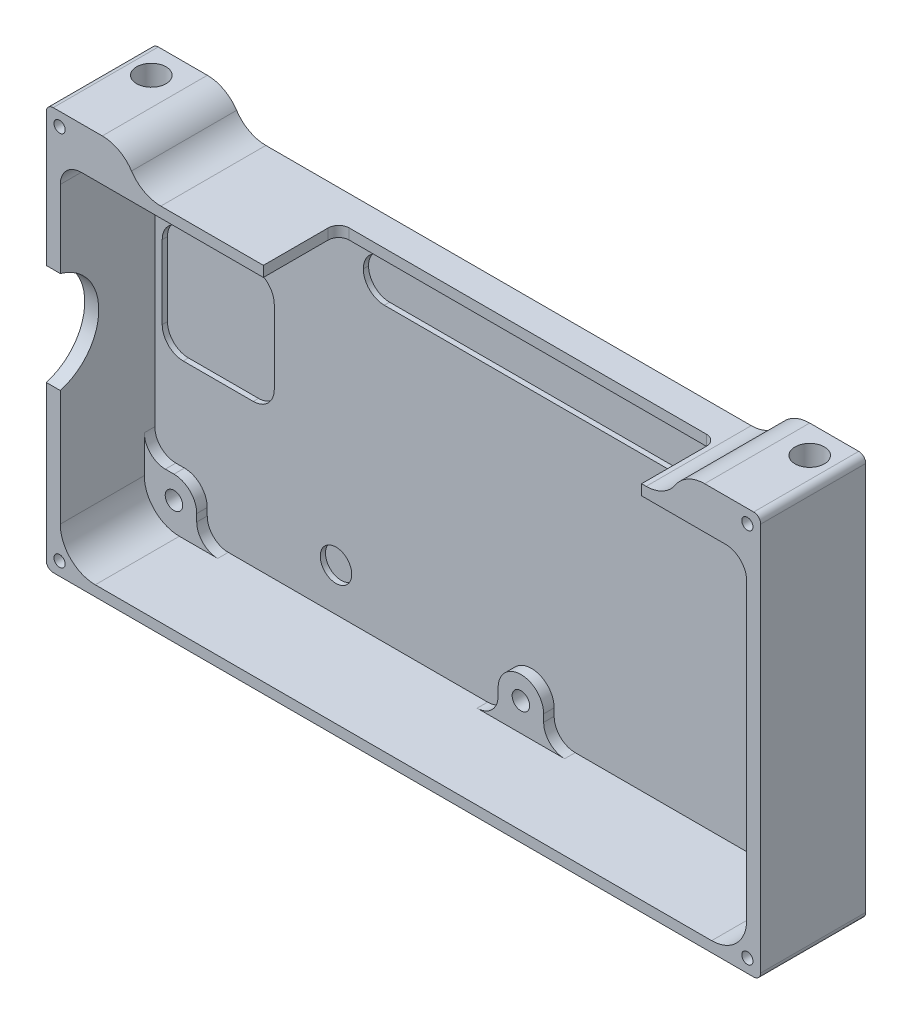
SolidWorks part; units mm, degrees
material "7075-T6, Platte (SS)"
ref_plane "Ebene vorne" through (0, 0, 0) normal (0, 0, 1) x (1, 0, 0)
ref_plane "Ebene oben" through (0, 0, 0) normal (0, 1, 0) x (1, 0, 0)
ref_plane "Ebene rechts" through (0, 0, 0) normal (1, 0, 0) x (0, 0, -1)
sketch "Skizze1" plane through (0, 0, 0) normal (0, 0, 1) x (1, 0, 0)
  line L1 (0, 0) -> (102, 0)
  line L2 (0, 0) -> (0, 57.5)
  line L3 (0, 57.5) -> (102, 57.5)
  line L4 (102, 0) -> (102, 57.5)
  line L5 (2, 51.5) -> (100, 51.5) construction
  line L6 (2, 51.5) -> (2, 1.5)
  line L7 (2, 1.5) -> (100, 1.5) construction
  line L8 (100, 51.5) -> (100, 1.5) construction
  dimension "D1" = 2
  dimension "D2" = 2
  dimension "D3" = 6
  dimension "D4" = 1.5
  dimension "D5" = 50
  dimension "D6" = 98
extrude "Aufsatz-Linear austragen1" add sketch "Skizze1" along normal blind 15 contours L8 L5 L6 L7 | L2 L3 L4 L1
sketch "Skizze4" plane through (0, 0, 15) normal (0, 0, 1) x (1, 0, 0)
  line L0 (0, 57.5) -> (102, 57.5) construction
  line L1 (2, 51.5) -> (100, 51.5)
  line L2 (2, 51.5) -> (2, 1.5)
  line L3 (2, 1.5) -> (100, 1.5)
  line L4 (100, 51.5) -> (100, 1.5)
  line L5 (0, 0) -> (0, 57.5) construction
  line L6 (102, 0) -> (102, 57.5) construction
  line L7 (0, 0) -> (102, 0) construction
  dimension "D1" = 6
  dimension "D2" = 2
  dimension "D3" = 2
  dimension "D4" = 1.5
extrude "Schnitt-Linear austragen1" cut sketch "Skizze4" against normal blind 13.5
sketch "Skizze5" plane through (0, 0, 1.5) normal (0, 0, 1) x (1, 0, 0)
  line L0 (2, 1.5) -> (100, 1.5) construction
  line L2 (98.945, 50.63) -> (98.945, 51.5) construction
  line L3 (3.055, 2.37) -> (98.945, 2.37) construction
  line L4 (3.055, 2.37) -> (3.055, 50.63) construction
  line L5 (3.055, 50.63) -> (98.945, 50.63) construction
  line L6 (98.945, 2.37) -> (98.945, 50.63) construction
  line L7 (100, 51.5) -> (2, 51.5) construction
  line L8 (98.945, 2.37) -> (98.945, 1.5) construction
  line L9 (3.055, 50.63) -> (2, 50.63) construction
  line L10 (2, 51.5) -> (2, 1.5) construction
  line L11 (98.945, 50.63) -> (100, 50.63) construction
  line L12 (100, 1.5) -> (100, 51.5) construction
  line L13 (6.235, 5.55) -> (55.765, 5.55) construction
  line L14 (55.765, 5.55) -> (95.765, 5.55) construction
  line L15 (95.765, 5.55) -> (95.765, 47.45) construction
  line L16 (95.765, 47.45) -> (6.235, 47.45) construction
  line L17 (6.235, 47.45) -> (6.235, 5.55) construction
  circle A0 centre (6.235, 5.55) radius 3.25
  circle A1 centre (55.765, 5.55) radius 3.25
  circle A2 centre (95.765, 5.55) radius 3.25
  circle A3 centre (95.765, 47.45) radius 3.25
  circle A4 centre (6.235, 47.45) radius 3.25
  dimension "D8" = 6.5
  dimension "D1" = 3.18
  dimension "D2" = 3.18
  dimension "D3" = 92.71
  dimension "D4" = 95.89
  dimension "D5" = 48.26
  dimension "D6" = 52.71
  dimension "D7" = 3.18
extrude "Aufsatz-Linear austragen2" add sketch "Skizze5" along normal blind 1.5
sketch "Skizze11" plane through (0, 0, 0) normal (-1, 0, 0) x (0, 0, 1)
  line L0 (15, 0) -> (15, 57.5) construction
  line L2 (17, 37.75) -> (17, 22.75)
  line L5 (3, 44.2) -> (3, 50.7) construction
  line L6 (3, 44.2) -> (3, 50.7) construction
  arc A0 (17, 37.75) -> (17, 22.75) centre (17, 30.25) ccw
  point P11 (3, 47.45)
  dimension "D1" = 7.5
  dimension "D2" = 17.2
  dimension "D3" = 2
extrude "Schnitt-Linear austragen3" cut sketch "Skizze11" against normal up to next
sketch "Skizze12" plane through (0, 57.5, 0) normal (0, 1, 0) x (1, 0, 0)
  line L0 (85, -5.75) -> (85, -15)
  line L1 (0, -15) -> (102, -15) construction
  line L2 (85, -15) -> (31, -15)
  line L3 (31, -15) -> (31, -5.75)
  line L4 (32.5, -4.25) -> (83.5, -4.25)
  line L6 (92.515, -3) -> (99.015, -3) construction
  line L7 (92.515, -3) -> (99.015, -3) construction
  arc A0 (31, -5.75) -> (32.5, -4.25) centre (32.5, -5.75) cw
  arc A1 (85, -5.75) -> (83.5, -4.25) centre (83.5, -5.75) ccw
  point P11 (95.765, -3)
  dimension "D1" = 1.5
  dimension "D2" = 10.765
  dimension "D3" = 54
  dimension "D4" = 10.75
extrude "Schnitt-Linear austragen4" cut sketch "Skizze12" against normal up to next
sketch "Skizze13" plane through (0, 0, 1.5) normal (0, 0, 1) x (1, 0, 0)
  line L0 (6.235, 44.2) -> (2, 44.2)
  line L1 (9.485, 47.45) -> (9.485, 51.5)
  line L2 (9.485, 5.55) -> (9.485, 1.5)
  line L3 (6.235, 8.8) -> (2, 8.8)
  line L4 (2, 51.5) -> (2, 1.5)
  line L5 (2, 1.5) -> (100, 1.5)
  line L6 (100, 1.5) -> (100, 51.5)
  line L7 (100, 51.5) -> (2, 51.5)
  line L8 (2, 51.5) -> (2, 44.2)
  line L10 (100, 1.5) -> (100, 8.8)
  line L11 (100, 51.5) -> (92.515, 51.5)
  line L12 (59.015, 5.55) -> (59.015, 1.5)
  line L13 (52.515, 5.55) -> (52.515, 1.5)
  line L14 (95.765, 8.8) -> (100, 8.8)
  line L15 (92.515, 5.55) -> (92.515, 1.5)
  line L16 (92.515, 47.45) -> (92.515, 51.5)
  line L17 (95.765, 44.2) -> (100, 44.2)
  line L18 (9.485, 51.5) -> (2, 51.5)
  line L19 (100, 44.2) -> (100, 51.5)
  line L20 (92.515, 1.5) -> (100, 1.5)
  line L21 (52.515, 1.5) -> (59.015, 1.5)
  line L22 (2, 8.8) -> (2, 1.5)
  line L23 (2, 51.5) -> (2, 1.5) construction
  line L24 (2, 1.5) -> (100, 1.5) construction
  line L25 (9.485, 1.5) -> (2, 1.5)
  circle A0 centre (6.235, 47.45) radius 3.25 construction
  arc A1 (6.235, 44.2) -> (9.485, 47.45) centre (6.235, 47.45) ccw
  circle A2 centre (6.235, 5.55) radius 3.25 construction
  arc A3 (9.485, 5.55) -> (6.235, 8.8) centre (6.235, 5.55) ccw
  circle A4 centre (95.765, 5.55) radius 3.25 construction
  circle A5 centre (55.765, 5.55) radius 3.25 construction
  arc A6 (95.765, 8.8) -> (92.515, 5.55) centre (95.765, 5.55) ccw
  arc A7 (59.015, 5.55) -> (52.515, 5.55) centre (55.765, 5.55) ccw
  circle A8 centre (95.765, 47.45) radius 3.25 construction
  arc A9 (92.515, 47.45) -> (95.765, 44.2) centre (95.765, 47.45) ccw
  dimension "D1" = 0
extrude "Aufsatz-Linear austragen3" add sketch "Skizze13" along normal up to surface (1.5 mm away) up to face at (9.485, 47.45, 3)
hole_wizard "M3 Gewindebohrung1" positions "Skizze9" profile "Skizze8" tap size "M3" standard "DIN" end condition through all
sketch "Skizze9" plane through (0, 0, 3) normal (0, 0, 1) x (1, 0, 0)
  point P0 (6.235, 47.45)
  point P3 (6.235, 5.55)
  point P6 (55.765, 5.55)
  point P9 (95.765, 47.45)
  point P12 (95.765, 5.55)
sketch "Skizze8" plane through (6.235, 47.45, 3) normal (1, 0, 0) x (0, -1, 0)
  line L0 (0, 0) -> (0, 3)
  line L1 (0, 3) -> (1.25, 3)
  line L2 (1.25, 3) -> (1.25, 0)
  line L5 (1.25, 0) -> (0, 0)
  line L11 (0, -6.35) -> (0, 107.95) construction
  dimension "Bohrerdurchmesser" = 2.5
  dimension "Bohrungstiefe" = 3
cosmetic thread "Bohrungsgewinde3" parameters "D2"=3
cosmetic thread "Bohrungsgewinde4" parameters "D2"=3
cosmetic thread "Bohrungsgewinde5" parameters "D2"=3
cosmetic thread "Bohrungsgewinde6" parameters "D2"=3
cosmetic thread "Bohrungsgewinde7" parameters "D2"=3
hole_wizard "Gewindebohrung für M4x0.7 Helicoil1" positions "Skizze7" profile "Skizze6" tap size "M4x0.7" standard "Helicoil® Metrisch"
sketch "Skizze7" plane through (38.5152, 57.5, 4.646) normal (0, -1, 0) x (-1, 0, 0)
  line L0 (34.5152, 0.646) -> (-59.4848, 0.646)
  line L4 (38.5152, 4.646) -> (-63.4848, 4.646) construction
  line L5 (38.5152, -10.354) -> (38.5152, 4.646) construction
  line L6 (-63.4848, -10.354) -> (-63.4848, 4.646) construction
  point P0 (34.5152, 0.646)
  point P2 (-59.4848, 0.646)
  dimension "D1" = 4
  dimension "D2" = 4
  dimension "D3" = 4
sketch "Skizze6" plane through (4, 57.5, 4) normal (1, 0, 0) x (0, 0, 1)
  line L0 (0, 0) -> (0, 5.2618)
  line L1 (0, 5.2618) -> (2.1, 4)
  line L2 (2.1, 4) -> (2.1, 0)
  line L5 (2.1, 0) -> (0, 0)
  line L10 (0, 5.2618) -> (-2.1, 4) construction
  line L11 (0, -6.35) -> (0, 107.95) construction
  dimension "Bohrerdurchmesser" = 4.2
  dimension "Bohrungstiefe" = 4
  dimension "Spitzenwinkel" = 118
cosmetic thread "Bohrungsgewinde12" parameters "D1"=0, "D2"=5.2
cosmetic thread "Bohrungsgewinde13" parameters "D1"=0, "D2"=5.2
fillet "Verrundung1" radius 5 2 edges at (2, 1.5, 9) (100, 1.5, 9)
fillet "Verrundung2" radius 3 10 edges at (92.515, 51.5, 2.25) (100, 44.2, 2.25) (100, 8.8, 2.25) (92.515, 1.5, 2.25) (59.015, 1.5, 2.25) (52.515, 1.5, 2.25) (2, 8.8, 2.25) (9.485, 1.5, 2.25) (9.485, 51.5, 2.25) (2, 44.2, 2.25)
fillet "Verrundung3" radius 1 4 edges at (0, 57.5, 7.5) (102, 57.5, 7.5) (102, 0, 7.5) (0, 0, 7.5)
ref_plane "Ebene1" through (51, 0, 0) normal (-1, 0, 0) x (0, 0, 1)
fillet "Verrundung4" radius 3 2 edges at (100, 51.5, 9) (2, 51.5, 9)
hole_wizard "M2 Gewindebohrung1" positions "Skizze18" profile "Skizze17" tap size "M2" standard "DIN"
sketch "Skizze18" plane through (0, 0, 15) normal (0, 0, 1) x (1, 0, 0)
  line L0 (1, 57.5) -> (31, 57.5) construction
  line L1 (0, 37.4784) -> (0, 56.5) construction
  line L2 (85, 57.5) -> (101, 57.5) construction
  line L3 (102, 1) -> (102, 56.5) construction
  line L4 (1, 0) -> (101, 0) construction
  line L5 (0, 1) -> (0, 23.0216) construction
  line L6 (1, 0) -> (101, 0) construction
  circle A0 centre (1.9, 55.6) radius 1.9
  circle A1 centre (100.1, 55.6) radius 1.9
  circle A2 centre (100.1, 1.9) radius 1.9
  circle A3 centre (1.9, 1.9) radius 1.9
  point P1 (1.9, 55.6)
  point P11 (100.1, 55.6)
  point P13 (100.1, 1.9)
  point P15 (1.9, 1.9)
  dimension "D1" = 3.8
sketch "Skizze17" plane through (1.9, 55.6, 15) normal (1, 0, 0) x (0, -1, 0)
  line L0 (0, 0) -> (0, 6.4807)
  line L1 (0, 6.4807) -> (0.8, 6)
  line L2 (0.8, 6) -> (0.8, 0)
  line L5 (0.8, 0) -> (0, 0)
  line L10 (0, 6.4807) -> (-0.8, 6) construction
  line L11 (0, -6.35) -> (0, 107.95) construction
  dimension "Bohrerdurchmesser" = 1.6
  dimension "Bohrungstiefe" = 6
  dimension "Spitzenwinkel" = 118
cosmetic thread "Bohrungsgewinde8" parameters "D1"=4, "D2"=2
cosmetic thread "Bohrungsgewinde9" parameters "D1"=4, "D2"=2
cosmetic thread "Bohrungsgewinde10" parameters "D1"=4, "D2"=2
cosmetic thread "Bohrungsgewinde11" parameters "D1"=4, "D2"=2
sketch "Skizze19" plane through (0, 0, 15) normal (0, 0, 1) x (1, 0, 0)
  line L0 (94, 57.5) -> (8, 57.5)
  line L1 (85, 57.5) -> (101, 57.5) construction
  line L2 (1, 57.5) -> (31, 57.5) construction
  line L3 (16.3516, 53) -> (85.6484, 53)
  line L5 (31, 51.5) -> (5, 51.5) construction
  line L6 (0, 37.4784) -> (0, 56.5) construction
  line L7 (102, 1) -> (102, 56.5) construction
  arc A0 (94, 57.5) -> (89.8242, 55.25) centre (94, 52.5) ccw
  arc A1 (85.6484, 53) -> (89.8242, 55.25) centre (85.6484, 58) ccw
  arc A2 (12.1758, 55.25) -> (8, 57.5) centre (8, 52.5) ccw
  arc A3 (16.3516, 53) -> (12.1758, 55.25) centre (16.3516, 58) cw
  dimension "D1" = 5
  dimension "D2" = 1.5
  dimension "D3" = 8
  dimension "D4" = 8
extrude "Schnitt-Linear austragen5" cut sketch "Skizze19" against normal through all
sketch "Skizze20" plane through (0, 0, 0) normal (0, 0, -1) x (-1, 0, 0)
  line L0 (-51, 0) -> (-51, -8) construction
  line L1 (-1, 0) -> (-101, 0) construction
  line L2 (-47, -8) -> (-51, -8)
  line L3 (-51, -8) -> (-55, -8)
  line L4 (-47, -8) -> (-47, 0)
  line L5 (-47, 0) -> (-55, 0)
  line L6 (-55, -8) -> (-55, 0)
  circle A0 centre (-51, -4) radius 2.25
  dimension "D3" = 4.5
  dimension "D1" = 8
  dimension "D2" = 8
extrude "Aufsatz-Linear austragen4" add sketch "Skizze20" against normal blind 3
fillet "Verrundung5" radius 3 4 edges at (55, 0, 1.5) (47, 0, 1.5) (47, -8, 1.5) (55, -8, 1.5)
sketch "Skizze21" plane through (0, 0, 1.5) normal (0, 0, 1) x (1, 0, 0)
  line L0 (89.465, 7.6) -> (27.865, 7.6) construction
  line L1 (83.765, 43.2) -> (31.765, 43.2)
  line L2 (83.765, 43.2) -> (83.765, 49.2)
  line L3 (83.765, 49.2) -> (31.765, 49.2)
  line L4 (31.765, 43.2) -> (31.765, 49.2)
  line L5 (19.055, 21.95) -> (3.055, 21.95)
  line L6 (19.055, 21.95) -> (19.055, 38.45)
  line L7 (19.055, 38.45) -> (3.055, 38.45)
  line L8 (3.055, 21.95) -> (3.055, 38.45)
  line L9 (100, 11.8) -> (100, 41.2) construction
  line L10 (100, 40.71) -> (94, 40.71)
  line L11 (100, 40.71) -> (100, 30.71)
  line L12 (100, 30.71) -> (94, 30.71)
  line L13 (94, 40.71) -> (94, 30.71)
  circle A0 centre (89.465, 7.6) radius 2.25
  circle A1 centre (27.865, 7.6) radius 2.25
  circle A2 centre (95.765, 47.45) radius 1.25 construction
  circle A3 centre (95.765, 47.45) radius 1.25 construction
  circle A4 centre (6.235, 47.45) radius 1.25 construction
  circle A5 centre (55.765, 5.55) radius 1.25 construction
  circle A6 centre (95.765, 5.55) radius 1.25 construction
  circle A7 centre (95.77, 47.46) radius 1.6 construction
  point P14 (83.765, 46.2)
  dimension "D8" = 9
  dimension "D10" = 4.5
  dimension "D1" = 52
  dimension "D2" = 6
  dimension "D3" = 12
  dimension "D4" = 1.25
  dimension "D5" = 16
  dimension "D6" = 16.5
  dimension "D7" = 3.18
  dimension "D9" = 61.6
  dimension "D11" = 2.05
  dimension "D12" = 6.3
  dimension "D13" = 10
  dimension "D14" = 6
  dimension "D15" = 6.75
extrude "Schnitt-Linear austragen6" cut sketch "Skizze21" against normal blind 0.75
fillet "Verrundung6" radius 3 12 edges at (3.055, 21.95, 1.125) (3.055, 38.45, 1.125) (19.055, 38.45, 1.125) (19.055, 21.95, 1.125) (31.765, 43.2, 1.125) (31.765, 49.2, 1.125) (83.765, 49.2, 1.125) (83.765, 43.2, 1.125) (100, 30.71, 1.125) (94, 30.71, 1.125) (94, 40.71, 1.125) (100, 40.71, 1.125)
